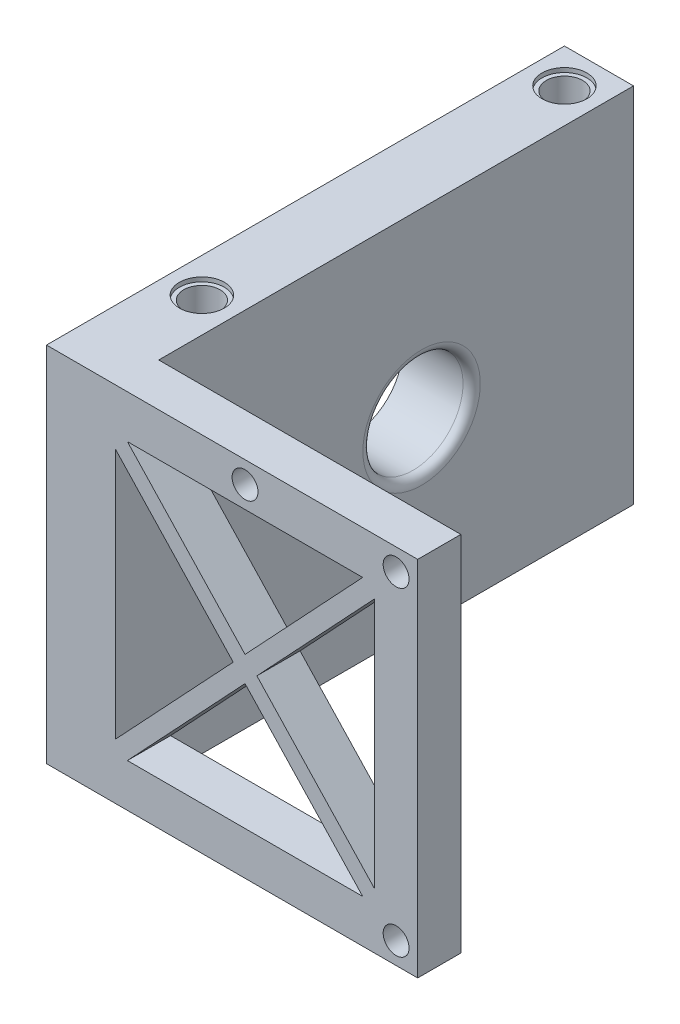
SolidWorks part; units mm, degrees
ref_plane "Front Plane" through (0, 0, 0) normal (0, 0, 1) x (1, 0, 0)
ref_plane "Top Plane" through (0, 0, 0) normal (0, 1, 0) x (1, 0, 0)
ref_plane "Right Plane" through (0, 0, 0) normal (1, 0, 0) x (0, 0, -1)
sketch "Sketch1" plane through (0, 0, 0) normal (0, 1, 0) x (1, 0, 0)
  line L1 (-10.223, 36.3848) -> (14.777, 36.3848)
  line L2 (-10.223, 36.3848) -> (-10.223, -13.6152)
  line L3 (-10.223, -13.6152) -> (14.777, -13.6152)
  line L4 (14.777, 36.3848) -> (14.777, -13.6152)
  circle A0 centre (1.277, 11.3848) radius 3.4
  dimension "D3" = 6.8
  dimension "D1" = 50
  dimension "D2" = 25
  dimension "D4" = 13.5
  dimension "D5" = 25
extrude "Boss-Extrude1" add sketch "Sketch1" along normal blind 3
sketch "Sketch2" plane through (-10.223, 0, 0) normal (-1, 0, 0) x (0, 0, 1)
  line L0 (18.15, 0) -> (-18.15, 0) construction
  line L1 (-36.3848, 3) -> (13.6152, 3)
  line L2 (-36.3848, 3) -> (-36.3848, 0)
  line L3 (-36.3848, 0) -> (13.6152, 0)
  line L4 (13.6152, 3) -> (13.6152, 0)
  line L5 (13.6152, 3) -> (13.6152, 0) construction
extrude "Boss-Extrude2" add sketch "Sketch2" along normal blind 8
sketch "Sketch3" plane through (0, 0, 0) normal (0, -1, 0) x (1, 0, 0)
  line L0 (-18.223, 13.6152) -> (14.777, 13.6152) construction
  line L1 (-18.223, -36.3848) -> (-10.223, -36.3848)
  line L2 (-18.223, -36.3848) -> (-18.223, 13.6152)
  line L3 (-18.223, 13.6152) -> (-10.223, 13.6152)
  line L4 (-10.223, -36.3848) -> (-10.223, 13.6152)
  dimension "D1" = 8
extrude "Boss-Extrude3" add sketch "Sketch3" along normal blind 42
sketch "Sketch4" plane through (0, 3, 0) normal (0, 1, 0) x (1, 0, 0)
  line L0 (-18.223, -13.6152) -> (-18.223, 36.3848) construction
  line L1 (14.777, 36.3848) -> (-18.223, 36.3848) construction
  line L2 (-18.223, -13.6152) -> (14.777, -13.6152) construction
  circle A0 centre (-14.223, 32.3848) radius 2.65
  circle A1 centre (-14.223, -9.6152) radius 2.65
  dimension "D2" = 5.3
  dimension "D4" = 5.3
  dimension "D5" = 4
  dimension "D6" = 4
  dimension "D1" = 4
  dimension "D3" = 4
extrude "Cut-Extrude1" cut sketch "Sketch4" against normal blind 0.5
ref_plane "Plane1" through (0, -19.5, 0) normal (0, 1, 0) x (1, 0, 0)
mirror "Mirror1" about plane through (0, -19.5, 0) normal (0, 1, 0) of "Cut-Extrude1"
sketch "Sketch5" plane through (-18.223, 0, 0) normal (-1, 0, 0) x (0, 0, 1)
  line L0 (18.15, 0) -> (-18.15, 0) construction
  line L1 (-6.9841, -24.1818) -> (-6.6547, -18.3888) construction
  line L2 (-6.6547, -18.3888) -> (-11.5069, -15.207) construction
  line L3 (-11.5069, -15.207) -> (-16.6885, -17.8182) construction
  line L4 (-16.6885, -17.8182) -> (-17.0179, -23.6112) construction
  line L5 (-17.0179, -23.6112) -> (-12.1657, -26.793) construction
  line L6 (-12.1657, -26.793) -> (-6.9841, -24.1818) construction
  circle A0 centre (-11.8363, -21) radius 5.025 construction
  circle A1 centre (-11.8363, -21) radius 5.8024
  dimension "D1" = 21
  dimension "D2" = 10.05
extrude "Cut-Extrude2" cut sketch "Sketch5" against normal blind 9
fillet "Fillet2" radius 1 1 edges at (-10.223, -21, -6.0339)
ref_plane "Plane2" through (-1.723, 0, 0) normal (-1, 0, 0) x (0, 0, 1)
mirror "Mirror2" about plane through (-1.723, 0, 0) normal (-1, 0, 0) of "Cut-Extrude1"
sketch "Sketch6" plane through (0, 3, 0) normal (0, 1, 0) x (1, 0, 0)
  line L0 (1.277, 14.7848) -> (1.277, 7.9848) construction
  line L1 (14.777, -13.6152) -> (14.777, 36.3848) construction
  line L2 (14.777, 16.9444) -> (14.777, 5.8251)
  circle A0 centre (1.277, 11.3848) radius 3.4 construction
  circle A1 centre (1.277, 11.3848) radius 3.1
  circle A2 centre (1.277, 11.3848) radius 12.6
  arc A3 (14.777, 16.9444) -> (14.777, 5.8251) centre (1.277, 11.3848) ccw
  line M9 (14.777, -13.6152) -> (14.777, 36.3848)
  dimension "D1" = 25.2
  dimension "D2" = 2
extrude "Boss-Extrude4" add sketch "Sketch6" along normal blind 2 contours A3 A2 M9
fillet "Fillet4" radius 1 1 edges at (14.777, 5, -11.3848)
sketch "Sketch8" plane through (0, 3, 0) normal (0, 1, 0) x (1, 0, 0)
  line L0 (4.677, 11.3848) -> (-2.123, 11.3848) construction
  circle A0 centre (1.277, 11.3848) radius 3.4 construction
  circle A1 centre (1.277, 19.8848) radius 1.5898
  circle A2 centre (1.277, 2.8848) radius 1.7774
  point P9 (1.277, 11.3848)
  dimension "D1" = 8.5
  dimension "D2" = 8.5
extrude "Cut-Extrude3" cut sketch "Sketch8" against normal blind 10
sketch "Sketch9" plane through (0, 0, 13.6152) normal (0, 0, 1) x (1, 0, 0)
  line L1 (14.777, 0) -> (-34.2447, 0)
  line L2 (14.777, 0) -> (14.777, 20.9769)
  line L3 (14.777, 20.9769) -> (-34.2447, 20.9769)
  line L4 (-34.2447, 0) -> (-34.2447, 20.9769)
extrude "Cut-Extrude4" cut sketch "Sketch9" against normal through all
ref_plane "Plane3" through (0, 0, -11.3848) normal (0, 0, 1) x (1, 0, 0)
sketch "Sketch11" plane through (0, 0, 0) normal (0, 1, 0) x (1, 0, 0)
  circle A2 centre (-14.223, 32.3848) radius 2.1
  dimension "D1" = 4.2
extrude "Cut-Extrude5" cut sketch "Sketch11" against normal through all contours A2
mirror "Mirror3" about plane through (0, 0, -11.3848) normal (0, 0, 1) of "Cut-Extrude5"
sketch "Sketch14" plane through (0, 0, 0) normal (0, 1, 0) x (1, 0, 0)
  circle A0 centre (-14.223, -9.6152) radius 2.6
  dimension "D1" = 5.2
extrude "Cut-Extrude6" cut sketch "Sketch14" against normal blind 0.5
mirror "Mirror4" about plane through (0, 0, -11.3848) normal (0, 0, 1) of "Cut-Extrude6"
sketch "Sketch15" plane through (0, 0, 13.6152) normal (0, 0, 1) x (1, 0, 0)
  line L1 (-10.223, -42) -> (-18.223, -42)
  line L2 (-10.223, -42) -> (-10.223, 0)
  line L3 (-10.223, 0) -> (-18.223, 0)
  line L4 (-18.223, -42) -> (-18.223, 0)
extrude "Boss-Extrude5" add sketch "Sketch15" along normal blind 10
sketch "Sketch17" plane through (-10.223, 0, 0) normal (1, 0, 0) x (0, 0, -1)
  line L0 (36.3848, -42) -> (-23.6152, -42) construction
  line L1 (-23.6152, 0) -> (-18.6152, 0)
  line L2 (-23.6152, 0) -> (-23.6152, -42)
  line L3 (-23.6152, -42) -> (-18.6152, -42)
  line L4 (-18.6152, 0) -> (-18.6152, -42)
  dimension "D1" = 5
extrude "Boss-Extrude6" add sketch "Sketch17" along normal blind 35
sketch "Sketch21" plane through (0, 0, 23.6152) normal (0, 0, 1) x (1, 0, 0)
  line L0 (-10.223, -5) -> (19.777, -37) construction
  line L1 (-10.223, -5) -> (19.777, -5)
  line L2 (-10.223, -5) -> (-10.223, -37)
  line L3 (-10.223, -37) -> (19.777, -37)
  line L4 (19.777, -5) -> (19.777, -37)
  line L5 (-10.223, -42) -> (-10.223, 0) construction
  line L6 (24.777, 0) -> (24.777, -42) construction
  line L7 (-18.223, -42) -> (24.777, -42) construction
  line L8 (24.777, 0) -> (-18.223, 0) construction
  line L9 (-10.223, -37) -> (19.777, -5) construction
  line L10 (-8.8523, -37) -> (4.777, -22.4621)
  line L11 (4.777, -22.4621) -> (18.4062, -37)
  line L12 (19.777, -35.5379) -> (6.1477, -21)
  line L13 (6.1477, -21) -> (19.777, -6.4621)
  line L14 (18.4062, -5) -> (4.777, -19.5379)
  line L15 (4.777, -19.5379) -> (-8.8523, -5)
  line L16 (-10.223, -6.4621) -> (3.4062, -21)
  line L17 (3.4062, -21) -> (-10.223, -35.5379)
  dimension "D1" = 5
  dimension "D2" = 5
  dimension "D3" = 5
  dimension "D4" = 1
  dimension "D5" = 1
  dimension "D6" = 1
  dimension "D7" = 1
extrude "Cut-Extrude7" cut sketch "Sketch21" against normal blind 5 contours L17 L16 L2 | L15 L14 L1 | L13 L12 L4 | L11 L10 L3
sketch "Sketch22" plane through (0, 0, 23.6152) normal (0, 0, 1) x (1, 0, 0)
  line L1 (24.777, 0) -> (24.777, -42) construction
  line L4 (-18.223, -42) -> (24.777, -42) construction
  line L5 (24.777, 0) -> (-18.223, 0) construction
  line L6 (4.777, -19.5379) -> (4.777, 0) construction
  circle A0 centre (22.277, -2.5) radius 1.5
  circle A1 centre (22.277, -39.5) radius 1.5
  circle A2 centre (4.777, -2.5) radius 1.5
  point P15 (0, 0)
  dimension "D5" = 3
  dimension "D6" = 3
  dimension "D7" = 3
  dimension "D1" = 2.5
  dimension "D2" = 2.5
  dimension "D3" = 2.5
  dimension "D4" = 2.5
extrude "Cut-Extrude8" cut sketch "Sketch22" against normal blind 5
chamfer "Chamfer1" distance 0.5 angle 45 3 edges at (23.777, -39.5, 18.6152) (6.277, -2.5, 18.6152) (23.777, -2.5, 18.6152)
